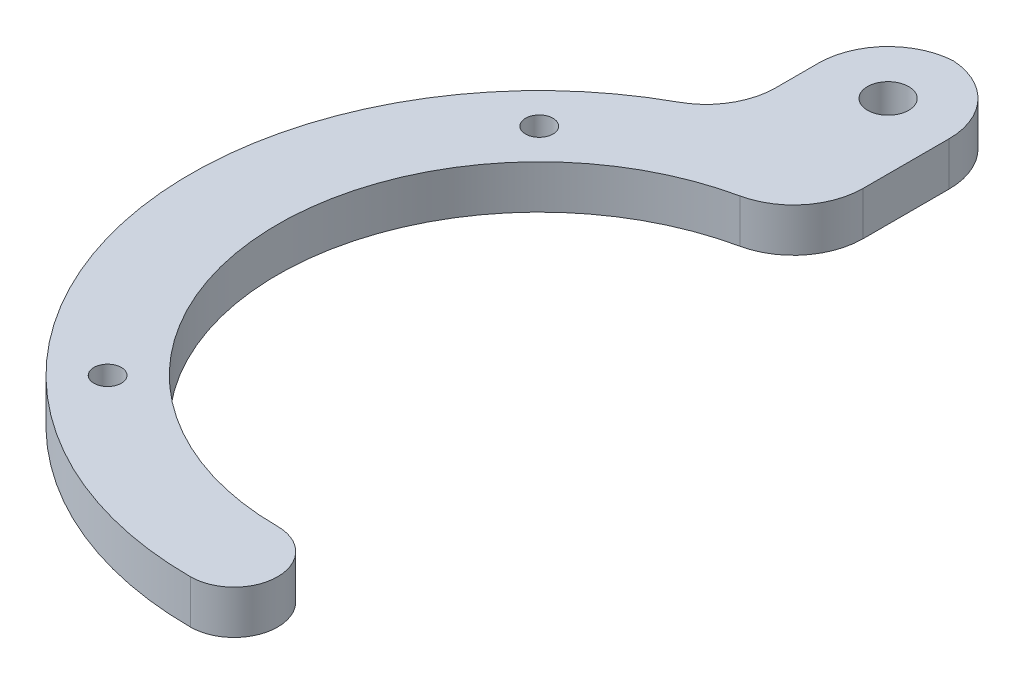
SolidWorks part; units mm, degrees
material "Pine"
ref_plane "Front Plane" through (0, 0, 0) normal (0, 0, 1) x (1, 0, 0)
ref_plane "Top Plane" through (0, 0, 0) normal (0, 1, 0) x (1, 0, 0)
ref_plane "Right Plane" through (0, 0, 0) normal (1, 0, 0) x (0, 0, -1)
sketch "Sketch1" plane through (0, 0, 0) normal (0, 1, 0) x (1, 0, 0)
  line L0 (0, 0) -> (19.05, 0)
  line L1 (19.05, 0) -> (19.05, -19.05)
  line L2 (0, 0) -> (0, -22.7571)
  line L3 (19.05, -19.05) -> (19.05, -120.65) construction
  line L4 (19.05, -31.75) -> (19.05, -19.05)
  line L5 (19.05, -9.525) -> (0, -9.525) construction
  line L6 (19.05, -69.85) -> (-12.3809, -38.4191) construction
  line L7 (19.05, -69.85) -> (-12.3809, -101.2809) construction
  arc A0 (19.05, -19.05) -> (19.05, -120.65) centre (19.05, -69.85) ccw
  arc A1 (19.05, -31.75) -> (19.05, -107.95) centre (19.05, -69.85) ccw
  arc A2 (19.05, -107.95) -> (19.05, -120.65) centre (19.05, -114.3) cw
  circle A3 centre (9.525, -9.525) radius 3
  circle A4 centre (19.05, -69.85) radius 44.45 construction
  circle A5 centre (-12.3809, -38.4191) radius 2
  circle A6 centre (-12.3809, -101.2809) radius 2
  dimension "D2" = 76.2
  dimension "D5" = 6
  dimension "D6" = 88.9
  dimension "D7" = 4
  dimension "D8" = 4
  dimension "D1" = 12.7
  dimension "D3" = 19.05
  dimension "D4" = 19.05
  dimension "D9" = 135
  dimension "D10" = 45
extrude "Boss-Extrude1" add sketch "Sketch1" along normal blind 6.35 contours L3 A1 L4 A0 | A0 L1 L0 L2 | A2 L3 region at (9.525, 0, 0.2968) region at (9.569, 0, 21.1296)
fillet "Fillet1" radius 10.16 4 edges at (0, 3.175, 22.7571) (19.05, 3.175, 31.75) (0, 3.175, 0) (19.05, 3.175, 0)
equation "\"D6@Sketch1\" = \"D2@Sketch1\" + \"D1@Sketch1\""
